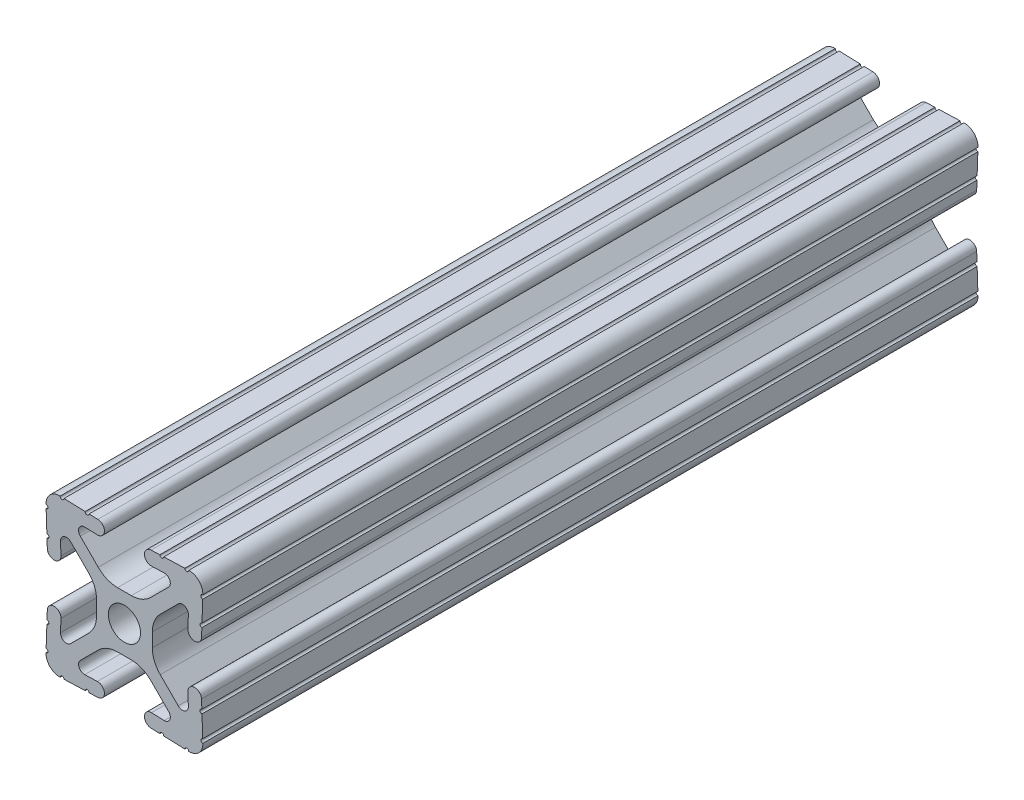
SolidWorks part; units mm, degrees
ref_plane "Front Plane" through (0, 0, 0) normal (0, 0, 1) x (1, 0, 0)
ref_plane "Top Plane" through (0, 0, 0) normal (0, 1, 0) x (1, 0, 0)
ref_plane "Right Plane" through (0, 0, 0) normal (1, 0, 0) x (0, 0, -1)
sketch "Sketch1" plane through (0, 0, 0) normal (0, 0, 1) x (1, 0, 0)
  line L0 (0, 12.7) -> (-12.7814, 12.7) construction
  line L1 (-4.5085, 0) -> (-4.5085, 2.9459)
  line L2 (-6.0437, 12.5461) -> (-10.0976, 12.6876) construction
  line L3 (-11.5616, 12.4229) -> (-4.3159, 12.1699) construction
  line L4 (-6.4364, 10.3486) -> (-6.3592, 12.5571) construction
  line L6 (-2.9459, 4.5085) -> (0, 4.5085)
  line L7 (0, 0) -> (0, 12.7) construction
  line L8 (0, 0) -> (-12.7814, 0) construction
  line L9 (0.7813, 0.7813) -> (-0.7813, -0.7813) construction
  line L10 (-2.9459, 4.5085) -> (-7.1484, 8.711)
  line L11 (-4.5085, 2.9459) -> (-8.711, 7.1484)
  line L13 (0, 0) -> (-12.7814, 12.7814) construction
  line L14 (-10.4131, 12.6987) -> (-4.3048, 12.4853)
  line L15 (-4.3048, 12.4853) -> (-4.382, 10.2769) construction
  line L16 (-4.382, 10.2769) -> (-6.4364, 10.3486)
  line L17 (-12.6987, 10.4131) -> (-12.4853, 4.3048)
  line L18 (-10.2769, 4.382) -> (-10.3486, 6.4364)
  circle A0 centre (0, 0) radius 2.6035
  arc A1 (-4.382, 10.2769) -> (-4.3048, 12.4853) centre (-4.3434, 11.3811) ccw
  arc A2 (-7.1484, 8.711) -> (-6.4364, 10.3486) centre (-6.4698, 9.3896) cw
  arc A3 (-8.711, 7.1484) -> (-10.3486, 6.4364) centre (-9.3896, 6.4698) ccw
  arc A4 (-10.2769, 4.382) -> (-12.4853, 4.3048) centre (-11.3811, 4.3434) cw
  arc A5 (-10.4131, 12.6987) -> (-12.6987, 10.4131) centre (-10.4902, 10.4902) ccw
  arc A6 (-10.4131, 12.6987) -> (-9.7821, 12.6766) centre (-10.0976, 12.6876) ccw
  arc A7 (-6.3592, 12.5571) -> (-5.7282, 12.5351) centre (-6.0437, 12.5461) ccw
  arc A8 (-12.5571, 6.3592) -> (-12.5351, 5.7282) centre (-12.5461, 6.0437) cw
  arc A9 (-12.6987, 10.4131) -> (-12.6766, 9.7821) centre (-12.6876, 10.0976) cw
  dimension "D1" = 5.207
  dimension "D5" = 14.859
  dimension "D9" = 2
  dimension "D2" = 25.4
  dimension "D12" = 0.6314
  dimension "D10" = 2.2098
  dimension "D3" = 9.017
  dimension "D4" = 9.017
  dimension "D6" = 25.4
  dimension "D7" = 6.477
  dimension "D8" = 2.2098
  dimension "D11" = 12.7
sketch "Sketch3" plane through (0, 0, 0) normal (0, 0, 1) x (1, 0, 0)
  line L0 (-2.9459, 4.5085) -> (0, 4.5085) construction
  line L1 (-2.9459, 4.5085) -> (-7.1484, 8.711) construction
  line L2 (-4.382, 10.2769) -> (-6.4364, 10.3486) construction
  line L3 (-10.4131, 12.6987) -> (-4.3048, 12.4853) construction
  line L4 (-4.5085, 0) -> (-4.5085, 2.9459) construction
  line L5 (-4.5085, 2.9459) -> (-8.711, 7.1484) construction
  line L6 (-10.2769, 4.382) -> (-10.3486, 6.4364) construction
  line L7 (-12.6987, 10.4131) -> (-12.4853, 4.3048) construction
  line L8 (-1.1153, 4.5085) -> (1.1153, 4.5085)
  line L9 (-4.2404, 5.803) -> (-7.1484, 8.711)
  line L10 (-4.382, 10.2769) -> (-6.4364, 10.3486)
  line L11 (-9.7821, 12.6766) -> (-6.3592, 12.5571)
  line L12 (-4.5085, -1.1153) -> (-4.5085, 1.1153)
  line L13 (-5.803, 4.2404) -> (-8.711, 7.1484)
  line L14 (-10.2769, 4.382) -> (-10.3486, 6.4364)
  line L15 (-12.6766, 9.7821) -> (-12.5571, 6.3592)
  line L16 (-5.7282, 12.5351) -> (-4.3048, 12.4853)
  line L17 (-12.5351, 5.7282) -> (-12.4853, 4.3048)
  line L18 (0, 0) -> (0, 12.7) construction
  line L19 (0, 0) -> (-12.7814, 0) construction
  line L20 (12.5351, 5.7282) -> (12.4853, 4.3048)
  line L21 (5.7282, 12.5351) -> (4.3048, 12.4853)
  line L22 (12.6766, 9.7821) -> (12.5571, 6.3592)
  line L23 (10.2769, 4.382) -> (10.3486, 6.4364)
  line L24 (5.803, 4.2404) -> (8.711, 7.1484)
  line L25 (4.5085, -1.1153) -> (4.5085, 1.1153)
  line L26 (9.7821, 12.6766) -> (6.3592, 12.5571)
  line L27 (4.382, 10.2769) -> (6.4364, 10.3486)
  line L28 (4.2404, 5.803) -> (7.1484, 8.711)
  line L29 (4.2404, -5.803) -> (7.1484, -8.711)
  line L30 (4.382, -10.2769) -> (6.4364, -10.3486)
  line L31 (9.7821, -12.6766) -> (6.3592, -12.5571)
  line L32 (5.803, -4.2404) -> (8.711, -7.1484)
  line L33 (10.2769, -4.382) -> (10.3486, -6.4364)
  line L34 (12.6766, -9.7821) -> (12.5571, -6.3592)
  line L35 (5.7282, -12.5351) -> (4.3048, -12.4853)
  line L36 (12.5351, -5.7282) -> (12.4853, -4.3048)
  line L37 (-12.5351, -5.7282) -> (-12.4853, -4.3048)
  line L38 (-5.7282, -12.5351) -> (-4.3048, -12.4853)
  line L39 (-12.6766, -9.7821) -> (-12.5571, -6.3592)
  line L40 (-10.2769, -4.382) -> (-10.3486, -6.4364)
  line L41 (-5.803, -4.2404) -> (-8.711, -7.1484)
  line L42 (-9.7821, -12.6766) -> (-6.3592, -12.5571)
  line L43 (-4.382, -10.2769) -> (-6.4364, -10.3486)
  line L44 (-4.2404, -5.803) -> (-7.1484, -8.711)
  line L45 (-1.1153, -4.5085) -> (1.1153, -4.5085)
  arc A0 (-10.4131, 12.6987) -> (-9.7821, 12.6766) centre (-10.0976, 12.6876) ccw construction
  arc A1 (-6.4364, 10.3486) -> (-7.1484, 8.711) centre (-6.4698, 9.3896) ccw construction
  arc A2 (-4.382, 10.2769) -> (-4.3048, 12.4853) centre (-4.3434, 11.3811) ccw construction
  arc A3 (-8.711, 7.1484) -> (-10.3486, 6.4364) centre (-9.3896, 6.4698) ccw construction
  arc A4 (-12.4853, 4.3048) -> (-10.2769, 4.382) centre (-11.3811, 4.3434) ccw construction
  arc A5 (-6.3592, 12.5571) -> (-5.7282, 12.5351) centre (-6.0437, 12.5461) ccw construction
  arc A6 (-10.4131, 12.6987) -> (-12.6987, 10.4131) centre (-10.4902, 10.4902) ccw construction
  arc A7 (-12.6766, 9.7821) -> (-12.6987, 10.4131) centre (-12.6876, 10.0976) ccw construction
  arc A8 (-12.5351, 5.7282) -> (-12.5571, 6.3592) centre (-12.5461, 6.0437) ccw construction
  arc A9 (-10.4131, 12.6987) -> (-9.7821, 12.6766) centre (-10.0976, 12.6876) ccw
  arc A10 (-6.4364, 10.3486) -> (-7.1484, 8.711) centre (-6.4698, 9.3896) ccw
  arc A11 (-4.382, 10.2769) -> (-4.3048, 12.4853) centre (-4.3434, 11.3811) ccw
  arc A12 (-8.711, 7.1484) -> (-10.3486, 6.4364) centre (-9.3896, 6.4698) ccw
  arc A13 (-12.4853, 4.3048) -> (-10.2769, 4.382) centre (-11.3811, 4.3434) ccw
  arc A14 (-6.3592, 12.5571) -> (-5.7282, 12.5351) centre (-6.0437, 12.5461) ccw
  arc A15 (-10.4131, 12.6987) -> (-12.6987, 10.4131) centre (-10.4902, 10.4902) ccw
  arc A16 (-12.6766, 9.7821) -> (-12.6987, 10.4131) centre (-12.6876, 10.0976) ccw
  arc A17 (-12.5351, 5.7282) -> (-12.5571, 6.3592) centre (-12.5461, 6.0437) ccw
  arc A18 (-1.1153, 4.5085) -> (-4.2404, 5.803) centre (-1.1153, 8.9281) cw
  arc A19 (4.5085, 1.1153) -> (5.803, 4.2404) centre (8.9281, 1.1153) cw
  arc A20 (1.1153, 4.5085) -> (4.2404, 5.803) centre (1.1153, 8.9281) ccw
  arc A21 (-4.5085, 1.1153) -> (-5.803, 4.2404) centre (-8.9281, 1.1153) ccw
  arc A22 (12.5351, 5.7282) -> (12.5571, 6.3592) centre (12.5461, 6.0437) cw
  arc A23 (12.6766, 9.7821) -> (12.6987, 10.4131) centre (12.6876, 10.0976) cw
  arc A24 (10.4131, 12.6987) -> (12.6987, 10.4131) centre (10.4902, 10.4902) cw
  arc A25 (6.3592, 12.5571) -> (5.7282, 12.5351) centre (6.0437, 12.5461) cw
  arc A26 (12.4853, 4.3048) -> (10.2769, 4.382) centre (11.3811, 4.3434) cw
  arc A27 (8.711, 7.1484) -> (10.3486, 6.4364) centre (9.3896, 6.4698) cw
  arc A28 (4.382, 10.2769) -> (4.3048, 12.4853) centre (4.3434, 11.3811) cw
  arc A29 (6.4364, 10.3486) -> (7.1484, 8.711) centre (6.4698, 9.3896) cw
  arc A30 (10.4131, 12.6987) -> (9.7821, 12.6766) centre (10.0976, 12.6876) cw
  arc A31 (10.4131, -12.6987) -> (9.7821, -12.6766) centre (10.0976, -12.6876) ccw
  arc A32 (6.4364, -10.3486) -> (7.1484, -8.711) centre (6.4698, -9.3896) ccw
  arc A33 (4.382, -10.2769) -> (4.3048, -12.4853) centre (4.3434, -11.3811) ccw
  arc A34 (8.711, -7.1484) -> (10.3486, -6.4364) centre (9.3896, -6.4698) ccw
  arc A35 (12.4853, -4.3048) -> (10.2769, -4.382) centre (11.3811, -4.3434) ccw
  arc A36 (6.3592, -12.5571) -> (5.7282, -12.5351) centre (6.0437, -12.5461) ccw
  arc A37 (10.4131, -12.6987) -> (12.6987, -10.4131) centre (10.4902, -10.4902) ccw
  arc A38 (12.6766, -9.7821) -> (12.6987, -10.4131) centre (12.6876, -10.0976) ccw
  arc A39 (12.5351, -5.7282) -> (12.5571, -6.3592) centre (12.5461, -6.0437) ccw
  arc A40 (-4.5085, -1.1153) -> (-5.803, -4.2404) centre (-8.9281, -1.1153) cw
  arc A41 (1.1153, -4.5085) -> (4.2404, -5.803) centre (1.1153, -8.9281) cw
  arc A42 (4.5085, -1.1153) -> (5.803, -4.2404) centre (8.9281, -1.1153) ccw
  arc A43 (-1.1153, -4.5085) -> (-4.2404, -5.803) centre (-1.1153, -8.9281) ccw
  arc A44 (-12.5351, -5.7282) -> (-12.5571, -6.3592) centre (-12.5461, -6.0437) cw
  arc A45 (-12.6766, -9.7821) -> (-12.6987, -10.4131) centre (-12.6876, -10.0976) cw
  arc A46 (-10.4131, -12.6987) -> (-12.6987, -10.4131) centre (-10.4902, -10.4902) cw
  arc A47 (-6.3592, -12.5571) -> (-5.7282, -12.5351) centre (-6.0437, -12.5461) cw
  arc A48 (-12.4853, -4.3048) -> (-10.2769, -4.382) centre (-11.3811, -4.3434) cw
  arc A49 (-8.711, -7.1484) -> (-10.3486, -6.4364) centre (-9.3896, -6.4698) cw
  arc A50 (-4.382, -10.2769) -> (-4.3048, -12.4853) centre (-4.3434, -11.3811) cw
  arc A51 (-6.4364, -10.3486) -> (-7.1484, -8.711) centre (-6.4698, -9.3896) cw
  arc A52 (-10.4131, -12.6987) -> (-9.7821, -12.6766) centre (-10.0976, -12.6876) cw
  circle A53 centre (0, 0) radius 2.6035 construction
  circle A54 centre (0, 0) radius 2.6035
  point P135 (4.5085, 0)
  dimension "D2" = 4.4196
extrude "Extrude1" add sketch "Sketch3" along normal mid plane 125.5
equation "\"D10@Sketch1\" = \"D8@Sketch1\""
equation "\"D11@Sketch1\" = \"D6@Sketch1\"/2"
equation "\"D12@Sketch1\" = \"D8@Sketch1\"/3.5"
equation "\"D2@Sketch3\" = \"D8@Sketch1\"*2"
